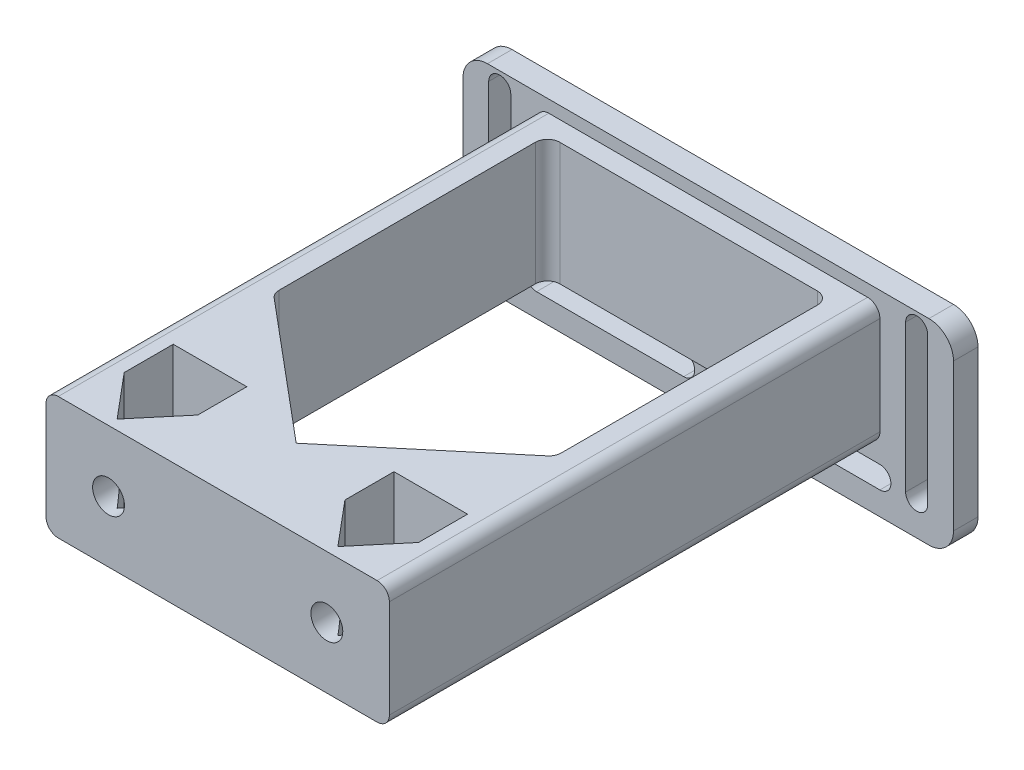
SolidWorks part; units mm, degrees
ref_plane "Front Plane" through (0, 0, 0) normal (0, 0, 1) x (1, 0, 0)
ref_plane "Top Plane" through (0, 0, 0) normal (0, 1, 0) x (1, 0, 0)
ref_plane "Right Plane" through (0, 0, 0) normal (1, 0, 0) x (0, 0, -1)
sketch "Sketch1" plane through (0, 0, 0) normal (0, 0, 1) x (1, 0, 0)
  line L1 (50, -20) -> (-50, -20)
  line L2 (50, -20) -> (50, 20)
  line L3 (50, 20) -> (-50, 20)
  line L4 (-50, -20) -> (-50, 20)
  line L5 (50, -20) -> (-50, 20) construction
  line L6 (50, 20) -> (-50, -20) construction
  point P0 (0, 0)
  dimension "D1" = 40
  dimension "D2" = 100
extrude "Boss-Extrude1" add sketch "Sketch1" along normal blind 5
sketch "Sketch2" plane through (0, 0, 5) normal (0, 0, 1) x (1, 0, 0)
  line L0 (-42.5, 17) -> (-42.5, -13) construction
  line L1 (-40.25, 17) -> (-40.25, -13)
  line L2 (-35, -13) -> (-5, -13) construction
  line L3 (-44.75, 17) -> (-44.75, -13)
  line L7 (42.5, 17) -> (42.5, -13) construction
  line L8 (44.75, 17) -> (44.75, -13)
  line L9 (40.25, 17) -> (40.25, -13)
  line L11 (5, -13) -> (35, -13) construction
  line L12 (5, -10.75) -> (35, -10.75)
  line L13 (5, -15.25) -> (35, -15.25)
  line L14 (-50, -20) -> (50, -20) construction
  line L15 (-50, 20) -> (-50, -20) construction
  line L16 (50, -20) -> (50, 20) construction
  line L17 (-35, -10.75) -> (-5, -10.75)
  line L18 (-35, -15.25) -> (-5, -15.25)
  arc A8 (-40.25, 17) -> (-44.75, 17) centre (-42.5, 17) ccw
  arc A9 (-44.75, -13) -> (-40.25, -13) centre (-42.5, -13) ccw
  arc A10 (44.75, 17) -> (40.25, 17) centre (42.5, 17) ccw
  arc A11 (40.25, -13) -> (44.75, -13) centre (42.5, -13) ccw
  arc A14 (5, -10.75) -> (5, -15.25) centre (5, -13) ccw
  arc A15 (35, -15.25) -> (35, -10.75) centre (35, -13) ccw
  arc A16 (-35, -10.75) -> (-35, -15.25) centre (-35, -13) ccw
  arc A17 (-5, -15.25) -> (-5, -10.75) centre (-5, -13) ccw
  point P2 (-42.5, 2)
  point P7 (-20, -13)
  point P10 (42.5, 2)
  point P21 (20, -13)
  dimension "D7" = 30
  dimension "D1" = 30
  dimension "D2" = 4.5
  dimension "D3" = 30
  dimension "D4" = 4.5
  dimension "D5" = 30
  dimension "D6" = 4.5
  dimension "D8" = 4.5
  dimension "D9" = 7
  dimension "D10" = 7
  dimension "D11" = 7.5
  dimension "D12" = 7.5
  dimension "D13" = 7.5
  dimension "D14" = 7.5
extrude "Cut-Extrude1" cut sketch "Sketch2" against normal blind 5 contours L1 A9 L3 A8
extrude "Cut-Extrude2" cut sketch "Sketch2<3>" against normal blind 5 contours L17 A17 L18 A16
sketch "Sketch2<3>" plane through (0, 0, 5) normal (0, 0, 1) x (1, 0, 0) same geometry as "Sketch2"
extrude "Cut-Extrude3" cut sketch "Sketch2<4>" against normal blind 5 contours L12 A15 L13 A14
sketch "Sketch2<4>" plane through (0, 0, 5) normal (0, 0, 1) x (1, 0, 0) same geometry as "Sketch2"
extrude "Cut-Extrude4" cut sketch "Sketch2<5>" against normal blind 5 contours L9 A11 L8 A10
sketch "Sketch2<5>" plane through (0, 0, 5) normal (0, 0, 1) x (1, 0, 0) same geometry as "Sketch2"
sketch "Sketch3" plane through (0, 0, 5) normal (0, 0, 1) x (1, 0, 0)
  line L0 (50, 20) -> (-50, 20) construction
  line L1 (35, -7.5) -> (-35, -7.5)
  line L2 (35, -7.5) -> (35, 17.5)
  line L3 (35, 17.5) -> (-35, 17.5)
  line L4 (-35, -7.5) -> (-35, 17.5)
  line L5 (35, -7.5) -> (-35, 17.5) construction
  line L6 (35, 17.5) -> (-35, -7.5) construction
  point P0 (0, 5)
  point P8 (0, 20)
  dimension "D1" = 25
  dimension "D2" = 70
  dimension "D3" = 2.5
extrude "Boss-Extrude2" add sketch "Sketch3" along normal blind 100
fillet "Fillet1" radius 5 4 edges at (-50, 20, 2.5) (50, 20, 2.5) (50, -20, 2.5) (-50, -20, 2.5)
fillet "Fillet2" radius 2.5 4 edges at (-35, 17.5, 55) (35, 17.5, 55) (35, -7.5, 55) (-35, -7.5, 55)
sketch "Sketch7" plane through (0, -7.5, 0) normal (0, -1, 0) x (1, 0, 0)
sketch "Sketch8" plane through (0, -7.5, 0) normal (0, -1, 0) x (1, 0, 0)
  line L0 (-28.75, 9) -> (28.75, 9)
  line L1 (28.75, 9) -> (28.75, 64.8759)
  line L2 (-28.75, 9) -> (-28.75, 64.8759)
  line L3 (-28.75, 64.8759) -> (0, 89)
  line L4 (0, 89) -> (28.75, 64.8759)
  line L5 (-32.5, 5) -> (32.5, 5) construction
  point P2 (0, 9)
  dimension "D1" = 50
  dimension "D2" = 4
  dimension "D3" = 80
  dimension "D4" = 57.5
extrude "Cut-Extrude8" cut sketch "Sketch8" against normal through all contours L2 L3 L4 L1 L0
fillet "Fillet3" radius 2.5 4 edges at (28.75, 5, 64.8759) (-28.75, 5, 64.8759) (28.75, 5, 9) (-28.75, 5, 9)
ref_plane "Plane1" through (0, 12.891, -0.5628) normal (0, 0.999, -0.0436) x (-1, 0, 0)
sketch "Sketch9" plane through (0, -7.5, 0) normal (0, -1, 0) x (1, 0, 0)
  line L0 (-30, 94.0618) -> (-30, 84.0618)
  line L1 (-30, 84.0618) -> (-15, 84.0618)
  line L2 (-15, 84.0618) -> (-15, 94.0618)
  line L3 (-15, 94.0618) -> (-22.5, 103)
  line L4 (-22.5, 103) -> (-30, 94.0618)
  line L5 (0, 105) -> (0, 89) construction
  line L6 (-32.5, 105) -> (32.5, 105) construction
  line L7 (15, 94.0618) -> (22.5, 103)
  line L8 (15, 84.0618) -> (15, 94.0618)
  line L9 (30, 84.0618) -> (15, 84.0618)
  line L10 (30, 94.0618) -> (30, 84.0618)
  line L11 (22.5, 103) -> (30, 94.0618)
  line L12 (-35, 5) -> (-35, 105) construction
  dimension "D1" = 40
  dimension "D2" = 40
  dimension "D3" = 15
  dimension "D4" = 10
  dimension "D5" = 2
  dimension "D6" = 5
extrude "Cut-Extrude9" cut sketch "Sketch9" against normal through all
sketch "Sketch10" plane through (0, 0, 105) normal (0, 0, 1) x (1, 0, 0)
  line L0 (-35, 15) -> (-35, -5) construction
  line L1 (0, -7.5) -> (0, 17.5) construction
  line L2 (-32.5, -7.5) -> (32.5, -7.5) construction
  line L3 (32.5, 17.5) -> (-32.5, 17.5) construction
  circle A0 centre (-22.2525, 5) radius 3.25
  circle A1 centre (22.2525, 5) radius 3.25
  point P4 (-35, 5)
  dimension "D1" = 6.5
  dimension "D2" = 12.7475
extrude "Cut-Extrude10" cut sketch "Sketch10" against normal up to next contours A1 | A0
